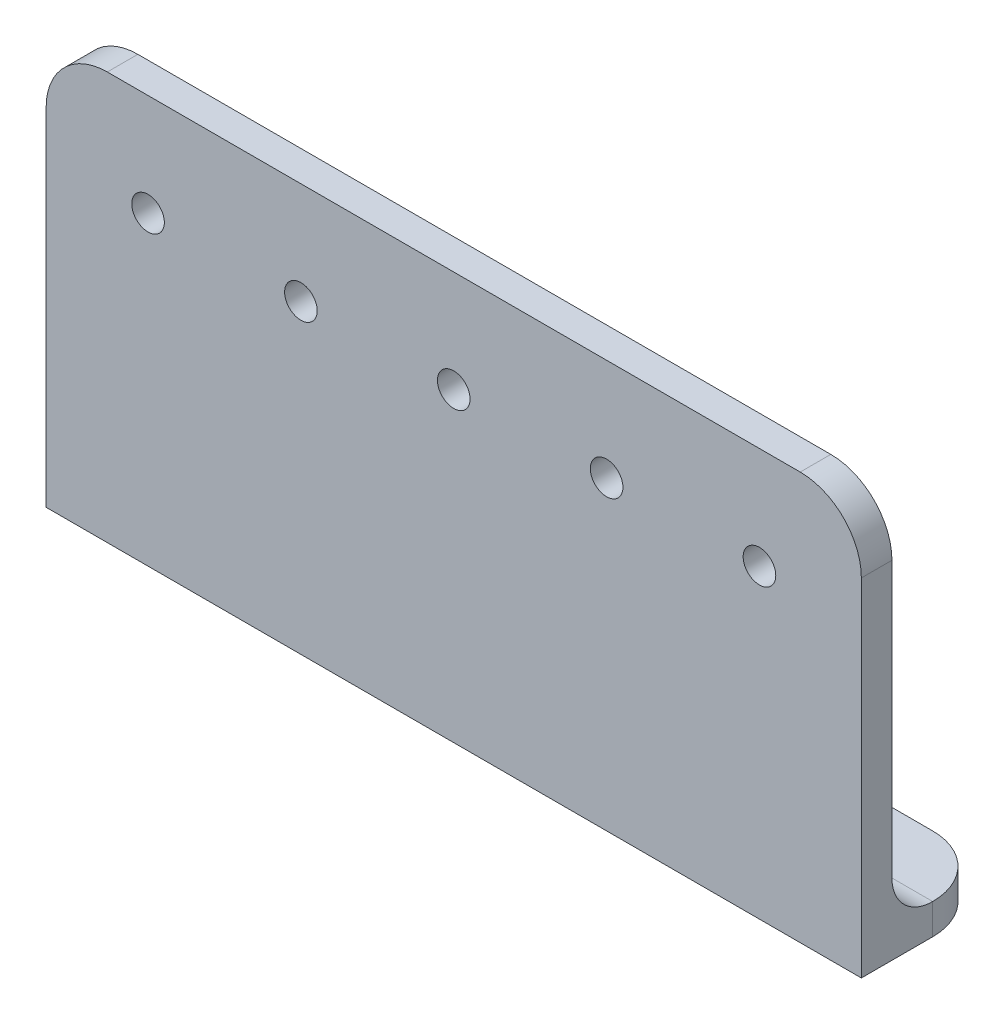
SolidWorks part; units mm, degrees
ref_plane "Front Plane" through (0, 0, 0) normal (0, 0, 1) x (1, 0, 0)
ref_plane "Top Plane" through (0, 0, 0) normal (0, 1, 0) x (1, 0, 0)
ref_plane "Right Plane" through (0, 0, 0) normal (1, 0, 0) x (0, 0, -1)
sketch "Sketch1" plane through (0, 0, 0) normal (0, 0, 1) x (1, 0, 0)
  line L1 (0, 0) -> (80, 0)
  line L2 (0, 0) -> (0, 40)
  line L3 (0, 40) -> (80, 40)
  line L4 (80, 0) -> (80, 40)
  dimension "D1" = 80
  dimension "D2" = 40
extrude "Boss-Extrude1" add sketch "Sketch1" along normal blind 3
sketch "Sketch2" plane through (0, 0, 3) normal (0, 0, 1) x (1, 0, 0)
  line L0 (10, 30) -> (25, 30) construction
  line L1 (25, 30) -> (40, 30) construction
  line L2 (40, 30) -> (55, 30) construction
  line L3 (55, 30) -> (70, 30) construction
  line L4 (80, 40) -> (0, 40) construction
  circle A0 centre (10, 30) radius 1.6
  circle A1 centre (25, 30) radius 1.6
  circle A2 centre (40, 30) radius 1.6
  circle A3 centre (55, 30) radius 1.6
  circle A4 centre (70, 30) radius 1.6
  point P12 (40, 40)
  dimension "D1" = 3.2
  dimension "D2" = 15
  dimension "D3" = 10
extrude "Cut-Extrude1" cut sketch "Sketch2" against normal through all
sketch "Sketch3" plane through (0, 0, 0) normal (0, 0, -1) x (-1, 0, 0)
  line L0 (-80, 0) -> (-80, 40) construction
  line L1 (-80, 3) -> (0, 3)
  line L2 (-80, 3) -> (-80, 0)
  line L3 (-80, 0) -> (0, 0)
  line L4 (0, 3) -> (0, 0)
  dimension "D1" = 3
extrude "Boss-Extrude2" add sketch "Sketch3" along normal blind 10
sketch "Sketch4" plane through (0, 3, 0) normal (0, 1, 0) x (1, 0, 0)
  line L0 (70, 7) -> (55, 7) construction
  line L1 (55, 7) -> (40, 7) construction
  line L2 (40, 7) -> (25, 7) construction
  line L3 (25, 7) -> (10, 7) construction
  line L4 (0, 10) -> (80, 10) construction
  circle A0 centre (70, 7) radius 1.6
  circle A1 centre (55, 7) radius 1.6
  circle A2 centre (40, 7) radius 1.6
  circle A3 centre (25, 7) radius 1.6
  circle A4 centre (10, 7) radius 1.6
  point P12 (40, 10)
  point P13 (0, 0)
  dimension "D1" = 3.2
  dimension "D2" = 15
  dimension "D3" = 3
extrude "Cut-Extrude2" cut sketch "Sketch4" against normal through all
fillet "Fillet1" radius 4 1 edges at (40, 3, 0)
fillet "Fillet2" radius 6 4 edges at (80, 40, 1.5) (0, 40, 1.5) (0, 1.5, -10) (80, 1.5, -10)
